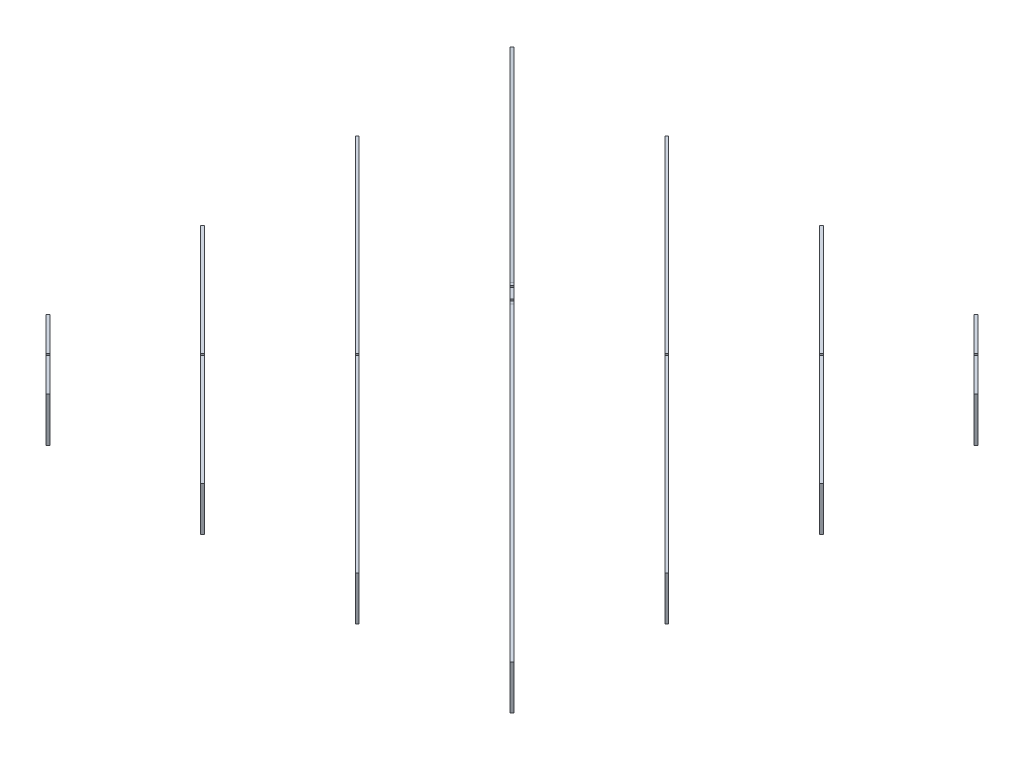
SolidWorks part; units mm, degrees
material "Plain Carbon Steel"
ref_plane "Front" through (0, 0, 0) normal (0, 0, 1) x (1, 0, 0)
ref_plane "Top" through (0, 0, 0) normal (0, 1, 0) x (1, 0, 0)
ref_plane "Right" through (0, 0, 0) normal (1, 0, 0) x (0, 0, -1)
sketch "Sketch1" plane through (0, 0, 0) normal (0, 1, 0) x (1, 0, 0)
  line L0 (-525, -525) -> (-525, 525) construction
  line L1 (-605, 605) -> (605, 605) construction
  line L2 (-605, 605) -> (-605, -605) construction
  line L3 (-605, -605) -> (605, -605) construction
  line L4 (605, 605) -> (605, -605) construction
  line L5 (-605, 605) -> (605, -605) construction
  line L6 (-605, -605) -> (605, 605) construction
  line L7 (-525, 525) -> (525, 525) construction
  line L8 (-525, 350) -> (525, 350) construction
  line L9 (-525, 175) -> (525, 175) construction
  line L10 (-525, 0) -> (525, 0) construction
  line L11 (-525, -175) -> (525, -175) construction
  line L12 (-525, -350) -> (525, -350) construction
  line L13 (-525, -525) -> (525, -525) construction
  line L14 (-350, -525) -> (-350, 525) construction
  line L15 (-175, -525) -> (-175, 525) construction
  line L16 (0, -525) -> (0, 525) construction
  line L17 (175, -525) -> (175, 525) construction
  line L18 (350, -525) -> (350, 525) construction
  line L19 (525, -525) -> (525, 525) construction
  line L20 (-525, -350) -> (-875, 0) construction
  line L21 (-875, 0) -> (-525, 350) construction
  line L22 (-875, 0) -> (-525, 0) construction
  point P0 (0, 0)
  dimension "D1" = 1210
  dimension "D2" = 1210
  dimension "D5" = 175
  dimension "D3" = 7
  dimension "D4" = 7
sketch "Sketch2" plane through (0, 0, 0) normal (0, 1, 0) x (1, 0, 0)
  line L0 (-605, 605) -> (605, -605) construction
  line L1 (602.8787, -602.8787) -> (-602.8787, -602.8787) construction
  line L2 (602.8787, -602.8787) -> (602.8787, 602.8787) construction
  line L3 (602.8787, 602.8787) -> (-602.8787, 602.8787) construction
  line L4 (-602.8787, -602.8787) -> (-602.8787, 602.8787) construction
  line L5 (602.8787, -602.8787) -> (-602.8787, 602.8787) construction
  line L6 (602.8787, 602.8787) -> (-602.8787, -602.8787) construction
  line L7 (-252.8787, 602.8787) -> (602.8787, -252.8787) construction
  line L8 (97.1213, 602.8787) -> (602.8787, 97.1213) construction
  line L9 (447.1213, 602.8787) -> (602.8787, 447.1213) construction
  line L10 (-602.8787, 252.8787) -> (252.8787, -602.8787) construction
  line L11 (-602.8787, -97.1213) -> (-97.1213, -602.8787) construction
  line L12 (-602.8787, -447.1213) -> (-447.1213, -602.8787) construction
  line L13 (-605, -449.2426) -> (-449.2426, -605)
  line L14 (-605, -99.2426) -> (-99.2426, -605)
  line L15 (-605, 250.7574) -> (250.7574, -605)
  line L16 (605, -600.7574) -> (-600.7574, 605)
  line L17 (-255, 600.7574) -> (600.7574, -255)
  line L18 (95, 600.7574) -> (600.7574, 95)
  line L19 (445, 600.7574) -> (600.7574, 445)
  line L20 (-600.7574, -445) -> (-445, -600.7574)
  line L21 (-600.7574, -95) -> (-95, -600.7574)
  line L22 (-600.7574, 255) -> (255, -600.7574)
  line L23 (600.7574, -605) -> (-605, 600.7574)
  line L24 (-250.7574, 605) -> (605, -250.7574)
  line L25 (99.2426, 605) -> (605, 99.2426)
  line L26 (449.2426, 605) -> (605, 449.2426)
  line L27 (-605, 605) -> (605, 605) construction
  line L29 (-605, -449.2426) -> (-600.7574, -445)
  line L30 (-449.2426, -605) -> (-445, -600.7574)
  line L31 (-605, -99.2426) -> (-600.7574, -95)
  line L32 (-99.2426, -605) -> (-95, -600.7574)
  line L33 (-605, 250.7574) -> (-600.7574, 255)
  line L34 (250.7574, -605) -> (255, -600.7574)
  line L35 (605, -600.7574) -> (600.7574, -605)
  line L36 (-600.7574, 605) -> (-605, 600.7574)
  line L37 (-255, 600.7574) -> (-250.7574, 605)
  line L38 (600.7574, -255) -> (605, -250.7574)
  line L39 (95, 600.7574) -> (99.2426, 605)
  line L40 (600.7574, 95) -> (605, 99.2426)
  line L41 (445, 600.7574) -> (449.2426, 605)
  line L42 (600.7574, 445) -> (605, 449.2426)
  point P0 (0, 0)
extrude "Boss-Extrude1" add sketch "Sketch2" along normal blind 100
sketch "Sketch4" plane through (-2.1213, 0, 2.1213) normal (-0.7071, 0, 0.7071) x (0.7071, 0, 0.7071)
  line L0 (0, 100) -> (0, 220) construction
  line L1 (-110.1371, 100) -> (110.1371, 100) construction
  line L2 (-30, 220) -> (-852.5992, 100)
  line L3 (-852.5992, 100) -> (-30, 100)
  line L4 (-30, 100) -> (-30, 220) construction
  line L5 (30, 220) -> (-30, 220)
  line L6 (852.5992, 100) -> (30, 100)
  line L7 (30, 220) -> (852.5992, 100)
  line L8 (-30, 100) -> (30, 100)
  dimension "D1" = 120
  dimension "D2" = 30
extrude "Boss-Extrude2" add sketch "Sketch4" against normal up to vertex (6 mm away) up to point (605, 100, 600.7574)
sketch "Sketch5" plane through (-527.1213, 0, 527.1213) normal (-0.7071, 0, 0.7071) x (0.7071, 0, 0.7071)
  line L0 (-742.4621, 0) -> (0, 0) construction
  line L1 (-745.4621, 50) -> (-739.4621, 50)
  line L2 (-745.4621, 50) -> (-745.4621, -50)
  line L3 (-745.4621, -50) -> (-739.4621, -50)
  line L4 (-739.4621, 50) -> (-739.4621, -50)
  line L5 (-745.4621, 50) -> (-739.4621, -50) construction
  line L6 (-745.4621, -50) -> (-739.4621, 50) construction
  line L7 (-855.5992, 0) -> (855.5992, 0) construction
  line L8 (247.4874, 0) -> (-494.9747, 0) construction
  line L9 (-497.9747, 50) -> (-491.9747, 50)
  line L10 (-497.9747, 50) -> (-497.9747, -50)
  line L11 (-497.9747, -50) -> (-491.9747, -50)
  line L12 (-491.9747, 50) -> (-491.9747, -50)
  line L13 (-497.9747, 50) -> (-491.9747, -50) construction
  line L14 (-497.9747, -50) -> (-491.9747, 50) construction
  line L15 (123.7437, 0) -> (-618.7184, 0) construction
  line L16 (-250.4874, 50) -> (-244.4874, 50)
  line L17 (-250.4874, 50) -> (-250.4874, -50)
  line L18 (-250.4874, -50) -> (-244.4874, -50)
  line L19 (-244.4874, 50) -> (-244.4874, -50)
  line L20 (-250.4874, 50) -> (-244.4874, -50) construction
  line L21 (-250.4874, -50) -> (-244.4874, 50) construction
  line L22 (0, 0) -> (0, 220) construction
  line L27 (30, 220) -> (-30, 220) construction
  line L28 (250.4874, -50) -> (244.4874, 50) construction
  line L29 (250.4874, 50) -> (244.4874, -50) construction
  line L30 (497.9747, -50) -> (491.9747, 50) construction
  line L31 (497.9747, 50) -> (491.9747, -50) construction
  line L32 (745.4621, -50) -> (739.4621, 50) construction
  line L33 (745.4621, 50) -> (739.4621, -50) construction
  line L34 (244.4874, 50) -> (244.4874, -50)
  line L35 (250.4874, -50) -> (244.4874, -50)
  line L36 (250.4874, 50) -> (250.4874, -50)
  line L37 (250.4874, 50) -> (244.4874, 50)
  line L38 (491.9747, 50) -> (491.9747, -50)
  line L39 (497.9747, -50) -> (491.9747, -50)
  line L40 (497.9747, 50) -> (497.9747, -50)
  line L41 (497.9747, 50) -> (491.9747, 50)
  line L42 (739.4621, 50) -> (739.4621, -50)
  line L43 (745.4621, -50) -> (739.4621, -50)
  line L44 (745.4621, 50) -> (745.4621, -50)
  line L45 (745.4621, 50) -> (739.4621, 50)
  circle A0 centre (-745.4621, 50) radius 1.5
  circle A1 centre (-739.4621, 50) radius 1.5
  circle A2 centre (-497.9747, 50) radius 1.5
  circle A3 centre (-491.9747, 50) radius 1.5
  circle A4 centre (-250.4874, 50) radius 1.5
  circle A5 centre (-244.4874, 50) radius 1.5
  circle A6 centre (244.4874, 50) radius 1.5
  circle A7 centre (250.4874, 50) radius 1.5
  circle A8 centre (491.9747, 50) radius 1.5
  circle A9 centre (497.9747, 50) radius 1.5
  circle A10 centre (739.4621, 50) radius 1.5
  circle A11 centre (745.4621, 50) radius 1.5
  point P0 (-742.4621, 0)
  point P9 (-494.9747, 0)
  point P16 (-247.4874, 0)
  point P52 (247.4874, 0)
  point P53 (494.9747, 0)
  point P54 (742.4621, 0)
  dimension "D7" = 3
  dimension "D8" = 3
  dimension "D9" = 3
  dimension "D10" = 3
  dimension "D11" = 3
  dimension "D12" = 3
  dimension "D1" = 3
  dimension "D2" = 3
  dimension "D3" = 3
  dimension "D4" = 100
  dimension "D5" = 100
  dimension "D6" = 100
extrude "Cut-Extrude2" cut sketch "Sketch5" against normal through all contours L1 A0 L2 | L4 A1 L1 | L1 A1 L4 | L2 A0 L1 | A1 L1 A0 L2 L3 L4 | L12 A3 L9 | L9 A3 L12 | A3 L9 A2 L10 L11 L12 | L10 A2 L9 | L9 A2 L10 | L16 A4 L17 | L19 A5 L16 | L16 A5 L19 | L17 A4 L16 | A5 L16 A4 L17 L18 L19 | A6 L34 L37 | A6 L37 L34 | L36 A7 L37 A6 L34 L35 | A7 L36 L37 | A7 L37 L36 | A8 L38 L41 | A8 L41 L38 | L40 A9 L41 A8 L38 L39 | A9 L40 L41 | A9 L41 L40 | A10 L42 L45 | A10 L45 L42 | L44 A11 L45 A10 L42 L43 | A11 L44 L45 | A11 L45 L44 region at (-1054.3927, 50.2122, -0.1501) region at (-1053.7925, 49.3634, 0.4502) region at (-1052.1213, -0.2925, 2.1213) region at (-1049.8499, 50.2122, 4.3927) region at (-1050.4502, 49.3634, 3.7925) region at (-879.3927, 50.2122, 174.8499) region at (-878.7925, 49.3634, 175.4502) region at (-877.1213, -0.2925, 177.1213) region at (-874.8499, 50.2122, 179.3927) region at (-875.4502, 49.3634, 178.7925) region at (-704.3927, 50.2122, 349.8499) region at (-703.7925, 49.3634, 350.4502) region at (-702.1213, -0.2925, 352.1213) region at (-699.8499, 50.2122, 354.3927) region at (-700.4502, 49.3634, 353.7925) region at (-353.7925, 49.3634, 700.4502) region at (-354.3927, 50.2122, 699.8499) region at (-352.1213, -0.2925, 702.1213) region at (-349.8499, 50.2122, 704.3927) region at (-350.4502, 49.3634, 703.7925) region at (-178.7925, 49.3634, 875.4502) region at (-179.3927, 50.2122, 874.8499) region at (-177.1213, -0.2925, 877.1213) region at (-174.8499, 50.2122, 879.3927) region at (-175.4502, 49.3634, 878.7925) region at (-3.7925, 49.3634, 1050.4502) region at (-4.3927, 50.2122, 1049.8499) region at (-2.1213, -0.2925, 1052.1213) region at (0.1501, 50.2122, 1054.3927) region at (-0.4502, 49.3634, 1053.7925)
sketch "Sketch6" plane through (-527.1213, 0, 527.1213) normal (-0.7071, 0, 0.7071) x (0.7071, 0, 0.7071)
  line L0 (-110.1371, 100) -> (110.1371, 100) construction
  line L1 (-3, 150) -> (3, 150)
  line L2 (-3, 150) -> (-3, 50)
  line L3 (-3, 50) -> (3, 50)
  line L4 (3, 150) -> (3, 50)
  line L5 (-3, 150) -> (3, 50) construction
  line L6 (-3, 50) -> (3, 150) construction
  line L7 (0, 100) -> (0, 0) construction
  circle A0 centre (-3, 50) radius 1.5
  circle A1 centre (3, 50) radius 1.5
  point P0 (0, 100)
  point P10 (0, 50)
  line M8 (110.1371, 100) -> (-110.1371, 100)
  dimension "D1" = 3
  dimension "D2" = 3
  dimension "D3" = 3
extrude "Cut-Extrude3" cut sketch "Sketch6" along normal up to surface (-989.9495 mm away) from surface contours A1 L4 L2 A0 L3 M8 | L3 A1 L4 | L2 A0 L3 | L3 A0 L2 | L4 A1 L3 region at (-527.1213, 75.2904, 527.1213) region at (-528.7925, 50.6366, 525.4502) region at (-529.3927, 49.7878, 524.8499) region at (-524.8499, 49.7878, 529.3927) region at (-525.4502, 50.6366, 528.7925) up to face at (172.8787, 35.803, -172.8787) starting at face at (527.1213, 50, -527.1213)
sketch "Sketch8" plane through (-527.1213, 0, 527.1213) normal (-0.7071, 0, 0.7071) x (0.7071, 0, 0.7071)
  line L4 (3, 150) -> (-3, 150)
  line L5 (3, 50) -> (3, 150)
  line L6 (-3, 50) -> (3, 50)
  line L7 (-3, 150) -> (-3, 50)
  line L8 (3, 150) -> (-3, 150)
  line L9 (3, 50) -> (3, 150)
  line L10 (-3, 50) -> (3, 50)
  line L11 (-3, 150) -> (-3, 50)
  circle A1 centre (3, 50) radius 1.5
  circle A2 centre (3, 50) radius 1.5
  circle A3 centre (-3, 50) radius 1.5
  circle A4 centre (-3, 50) radius 1.5
  line M9 (110.1371, 100) -> (-110.1371, 100)
  dimension "D1" = 0
  dimension "D2" = 0
  dimension "D3" = 0
extrude "Cut-Extrude4" cut sketch "Sketch8" against normal up to surface (500.9747 mm away) contours A4 L10 A2 L9 L11 M9 | L10 A2 L9 | L11 A4 L10 | L10 A4 L11 | L9 A2 L10 region at (-527.1213, 75.2904, 527.1213) region at (-524.8499, 49.7878, 529.3927) region at (-525.4502, 50.6366, 528.7925) region at (-528.7925, 50.6366, 525.4502) region at (-529.3927, 49.7878, 524.8499) up to face at (-172.8787, 35.803, 172.8787)
sketch "Sketch9" plane through (-2.1213, 0, 2.1213) normal (-0.7071, 0, 0.7071) x (0.7071, 0, 0.7071)
  line L0 (0, 0) -> (0, 220) construction
  line L1 (30, 220) -> (-30, 220) construction
  line L3 (-3, -110) -> (3, -110)
  line L4 (-3, -110) -> (-3, 110)
  line L5 (-3, 110) -> (3, 110)
  line L6 (3, -110) -> (3, 110)
  line L7 (-3, -110) -> (3, 110) construction
  line L8 (-3, 110) -> (3, -110) construction
  circle A0 centre (-3, 110) radius 1.5
  circle A1 centre (3, 110) radius 1.5
  point P9 (0, 110)
  line M18 (-244.4874, 0) -> (244.4874, 0)
  dimension "D1" = 3
  dimension "D2" = 3
  dimension "D3" = 3
extrude "Cut-Extrude5" cut sketch "Sketch9" against normal up to next (6 mm away) contours A1 L5 A0 L4 L6 M18 | L6 A1 L5 | L5 A0 L4 | L4 A0 L5 | L5 A1 L6 region at (-2.1213, 54.7073, 2.1213) region at (-4.3927, 110.2122, -0.1501) region at (-3.7925, 109.3634, 0.4502) region at (-0.4502, 109.3634, 3.7925) region at (0.1501, 110.2122, 4.3927)
sketch "Sketch10" plane through (-2.1213, 0, 2.1213) normal (-0.7071, 0, 0.7071) x (0.7071, 0, 0.7071)
  line L0 (0, 110) -> (0, 220) construction
  line L1 (-1.5, 110) -> (1.5, 110) construction
  line L2 (30, 220) -> (-30, 220) construction
  line L3 (-16, 220) -> (-22, 200) construction
  line L4 (16, 200) -> (22, 200)
  line L5 (16, 200) -> (16, 220)
  line L6 (16, 220) -> (22, 220)
  line L7 (22, 200) -> (22, 220)
  line L8 (16, 200) -> (22, 220) construction
  line L9 (16, 220) -> (22, 200) construction
  line L10 (-16, 200) -> (-22, 220) construction
  line L11 (-22, 200) -> (-22, 220)
  line L12 (-16, 220) -> (-22, 220)
  line L13 (-16, 200) -> (-16, 220)
  line L14 (-16, 200) -> (-22, 200)
  circle A0 centre (16, 200) radius 1.5
  circle A1 centre (22, 200) radius 1.5
  circle A2 centre (-22, 200) radius 1.5
  circle A3 centre (-16, 200) radius 1.5
  point P6 (19, 210)
  point P20 (-19, 210)
  line M29 (30, 220) -> (-30, 220)
  dimension "D1" = 3
  dimension "D3" = 3
  dimension "D4" = 3
  dimension "D2" = 20
  dimension "D5" = 32
extrude "Cut-Extrude6" cut sketch "Sketch10" against normal through all contours L4 A1 L7 | L7 A1 L4 | A1 L7 L5 A0 L4 M29 | L4 A0 L5 | L5 A0 L4 | A3 L13 L14 | A3 L14 L13 | L14 A3 L13 L11 A2 M29 | A2 L11 L14 | A2 L14 L11 region at (9.6425, 200.6366, 13.8852) region at (9.0423, 199.7878, 13.285) region at (11.3137, 210.2841, 15.5563) region at (-15.5563, 210.2841, -11.3137) region at (12.9849, 200.6366, 17.2275) region at (13.5851, 199.7878, 17.8277) region at (-13.285, 199.7878, -9.0423) region at (-13.8852, 200.6366, -9.6425) region at (-17.2275, 200.6366, -12.9849) region at (-17.8277, 199.7878, -13.5851)
sketch "Sketch11" plane through (-2.1213, 0, 2.1213) normal (-0.7071, 0, 0.7071) x (0.7071, 0, 0.7071)
  line L0 (-371.2311, 19) -> (-371.2311, 25) construction
  line L1 (-356.2311, 19) -> (-386.2311, 19) construction
  line L2 (-386.2311, 25) -> (-356.2311, 25) construction
  line L3 (-371.2311, 25) -> (-346.2311, 22) construction
  line L4 (-346.2311, 25) -> (-346.2311, 19) construction
  line L5 (-346.2311, 22) -> (-396.2311, 22) construction
  line L6 (-396.2311, 19) -> (-396.2311, 25) construction
  line L7 (0, 0) -> (0, 380.8547) construction
  line L8 (-343.2311, 16) -> (-399.2311, 16)
  line L9 (-343.2311, 16) -> (-343.2311, 28)
  line L10 (-343.2311, 28) -> (-399.2311, 28)
  line L11 (-399.2311, 16) -> (-399.2311, 28)
  line L12 (-343.2311, 16) -> (-399.2311, 28) construction
  line L13 (-343.2311, 28) -> (-399.2311, 16) construction
  line L14 (-244.4874, 0) -> (244.4874, 0) construction
  line L15 (343.2311, 28) -> (399.2311, 16) construction
  line L16 (343.2311, 16) -> (399.2311, 28) construction
  line L17 (346.2311, 22) -> (396.2311, 22) construction
  line L18 (371.2311, 25) -> (346.2311, 22) construction
  line L19 (371.2311, 19) -> (371.2311, 25) construction
  line L20 (399.2311, 16) -> (399.2311, 28)
  line L21 (343.2311, 28) -> (399.2311, 28)
  line L22 (343.2311, 16) -> (343.2311, 28)
  line L23 (343.2311, 16) -> (399.2311, 16)
  point P12 (-371.2311, 22)
  point P29 (371.2311, 22)
  dimension "D1" = 3
  dimension "D2" = 3
extrude "Cut-Extrude7" cut sketch "Sketch11" against normal up to next (6 mm away)
sketch "Sketch12" plane through (-2.1213, 0, 2.1213) normal (-0.7071, 0, 0.7071) x (0.7071, 0, 0.7071)
  line L0 (0, 0) -> (0, 383.9369) construction
  line L1 (123.7437, 74) -> (-123.7437, 74) construction
  circle A0 centre (123.7437, 64) radius 4
  circle A1 centre (123.7437, 84) radius 4
  circle A2 centre (-123.7437, 64) radius 4
  circle A3 centre (-123.7437, 84) radius 4
  circle A4 centre (40, 74) radius 10
  circle A5 centre (-40, 74) radius 10
  dimension "D1" = 8
  dimension "D2" = 20
  dimension "D3" = 80
extrude "Cut-Extrude8" cut sketch "Sketch12" against normal up to next (6 mm away)
sketch "Sketch13" plane through (177.1213, 0, -177.1213) normal (0.7071, 0, -0.7071) x (-0.7071, 0, -0.7071)
  line L0 (-371.2311, 0) -> (-371.2311, 100) construction
  line L1 (-491.9747, 0) -> (-250.4874, 0) construction
  line L2 (-605.1118, 100) -> (-3, 100) construction
  line L3 (371.2311, 0) -> (371.2311, 100) construction
  line L4 (250.4874, 0) -> (491.9747, 0) construction
  line L5 (3, 100) -> (605.1118, 100) construction
  line L6 (3, 100) -> (244.4874, 0) construction
  line L7 (-3, 100) -> (-244.4874, 0) construction
  circle A0 centre (371.2311, 50) radius 3
  circle A1 centre (123.7437, 50) radius 3
  circle A2 centre (-123.7437, 50) radius 3
  circle A3 centre (-371.2311, 50) radius 3
  dimension "D1" = 6
extrude "Cut-Extrude9" cut sketch "Sketch13" along normal up to surface (247.4874 mm away) from surface up to face at (352.1213, 45.4828, -352.1213) starting at face at (172.8787, 41.2313, -172.8787)
ref_plane "Plane1" through (0, 0, 0) normal (-0.7071, 0, 0.7071) x (0.7071, 0, 0.7071)
mirror "Mirror1" about plane through (0, 0, 0) normal (-0.7071, 0, 0.7071) of "Cut-Extrude9"
equation "\"D1@Boss-Extrude1\"=\"Plate width\""
equation "\"Plate width\"=100"
equation "\"D1@Sketch5\"=\"Half rib thickness\""
equation "\"D2@Sketch5\"=\"Half rib thickness\""
equation "\"D3@Sketch5\"=\"Half rib thickness\""
equation "\"D4@Sketch5\"=\"Plate width\""
equation "\"D5@Sketch5\"=\"Plate width\""
equation "\"D6@Sketch5\"=\"Plate width\""
equation "\"D7@Sketch5\"=\"Half rib thickness\""
equation "\"D8@Sketch5\"=\"Half rib thickness\""
equation "\"D9@Sketch5\"=\"Half rib thickness\""
equation "\"D10@Sketch5\"=\"Half rib thickness\""
equation "\"D11@Sketch5\"=\"Half rib thickness\""
equation "\"D12@Sketch5\"=\"Half rib thickness\""
equation "\"D1@Sketch6\"=\"Half rib thickness\""
equation "\"D2@Sketch6\"=\"Half rib thickness\""
equation "\"D3@Sketch6\"=\"Half rib thickness\""
equation "\"D1@Sketch9\"=\"Half rib thickness\""
equation "\"D2@Sketch9\"=\"Half rib thickness\""
equation "\"D3@Sketch9\"=\"Half rib thickness\""
equation "\"D1@Sketch10\"=\"Half rib thickness\""
equation "\"D3@Sketch10\"=\"Half rib thickness\""
equation "\"D4@Sketch10\"=\"Half rib thickness\""
